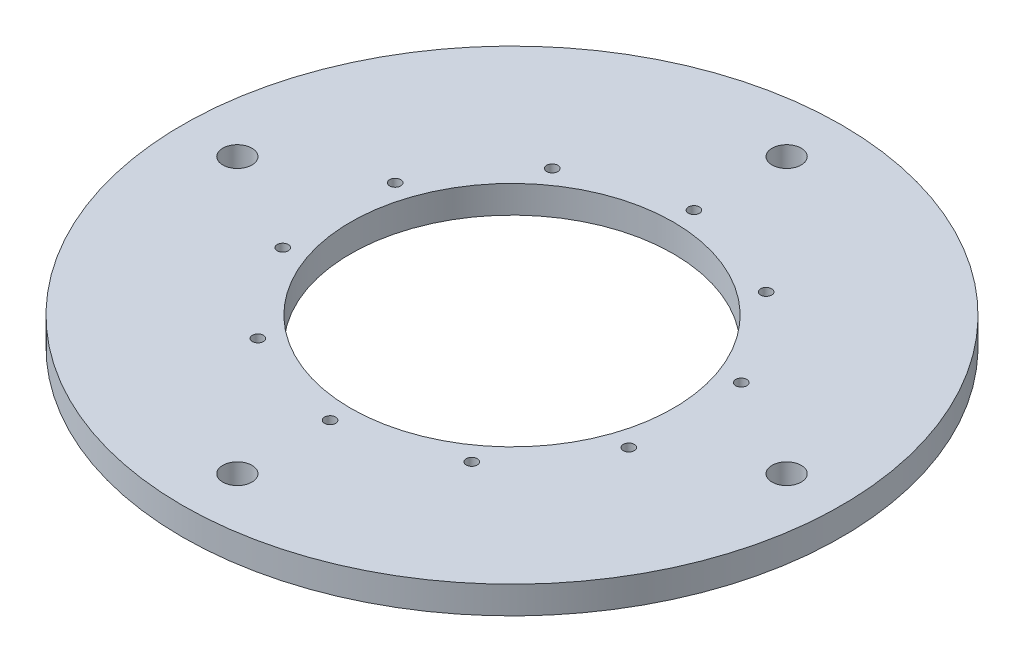
SolidWorks part; units mm, degrees
material "Plain Carbon Steel"
ref_plane "Front Plane" through (0, 0, 0) normal (0, 0, 1) x (1, 0, 0)
ref_plane "Top Plane" through (0, 0, 0) normal (0, 1, 0) x (1, 0, 0)
ref_plane "Right Plane" through (0, 0, 0) normal (1, 0, 0) x (0, 0, -1)
sketch "Sketch1" plane through (0, 0, 0) normal (0, 1, 0) x (1, 0, 0)
  circle A3 centre (0, 0) radius 152.4
  circle A8 centre (0, 0) radius 127 construction
  circle A20 centre (0, 0) radius 74.6125
  circle A23 centre (0, 0) radius 84.1375 construction
  point P2 (0, 127)
  point P5 (0, 84.1375)
  dimension "Diameter_Takeout_BoltCircle" = 254
  dimension "Diameter_ThrustPlate" = 304.8
  dimension "D2" = 168.275
  dimension "D4" = 149.225
extrude "ThrustPlate_TC3" add sketch "Sketch1" against normal blind 12.7 separate body contours A3 region at (-148.0895, 0, 0)
sketch "Sketch11" plane through (0, 0, 0) normal (0, 1, 0) x (1, 0, 0)
  point P0 (0, 127)
hole_wizard "UNDEF_Clearance_ThrustPlate" positions "Sketch11" profile "Sketch12" hole size "1/2" standard "ANSI Inch" end condition through all
sketch "Sketch12" plane through (0, 0, -127) normal (1, 0, 0) x (0, 0, 1)
  line L0 (0, 0) -> (0, 12.7)
  line L1 (0, 12.7) -> (6.7462, 12.7)
  line L2 (6.7462, 12.7) -> (6.7462, 0)
  line L5 (6.7462, 0) -> (0, 0)
  line L11 (0, -6.35) -> (0, 107.95) construction
  dimension "Thru Hole Dia." = 13.4925
  dimension "Thru Hole Depth" = 12.7
pattern_circular "Clearance_ThrustPlate_Pattern" count 4 over 360 about axis through (0, -12.7, 0) along (0, 1, 0) of "UNDEF_Clearance_ThrustPlate" reverse direction yes
sketch "Sketch22" plane through (0, 0, 0) normal (0, 1, 0) x (1, 0, 0)
  point P0 (0, 84.1375)
hole_wizard "#10 Clearance Hole1" positions "Sketch22" profile "Sketch23" hole size "#10" standard "ANSI Inch" end condition through all
sketch "Sketch23" plane through (0, 0, -84.1375) normal (1, 0, 0) x (0, 0, 1)
  line L0 (0, 0) -> (0, 12.7)
  line L1 (0, 12.7) -> (2.5527, 12.7)
  line L2 (2.5527, 12.7) -> (2.5527, 0)
  line L5 (2.5527, 0) -> (0, 0)
  line L11 (0, -6.35) -> (0, 107.95) construction
  dimension "Thru Hole Dia." = 5.1054
  dimension "Thru Hole Depth" = 12.7
pattern_circular "CirPattern1" count 10 over 360 about axis through (0, -12.7, 0) along (0, 1, 0) of "#10 Clearance Hole1" reverse direction yes
equation "\"Diameter_BackPlate\"= 6.5"
equation "\"VAR_Diameter_BackPlate_BoltCircle\"= 6"
equation "\"VAR_Diameter_FuelOuterPlenum\"= 4.4"
equation "\"Thickness_ThrustPlate\"= 0.5'undetermined"
equation "\"Diameter_ThrustPlate\"= 12'defined"
equation "\"Diameter_Takeout_BoltCicle\"= 10'defined"
equation "\"Diameter_Takeout_BoltCircle@Sketch1\"=\"Diameter_Takeout_BoltCicle\""
equation "\"Diameter_ThrustPlate@Sketch1\"=\"Diameter_ThrustPlate\""
equation "\"D1@ThrustPlate_TC3\"=\"Thickness_ThrustPlate\""
equation "\"VAR_Diameter_CBORE\"= 0.44'undetermined"
equation "\"VAR_Diameter_Clearance_ThrustPlate\"= 0.25'undetermined"
equation "\"NumberBolts_BackPlate\"= 20"
equation "\"NumberBolts_Takeout\"= 4'defined"
equation "\"D1@Clearance_ThrustPlate_Pattern\"=\"NumberBolts_Takeout\""
